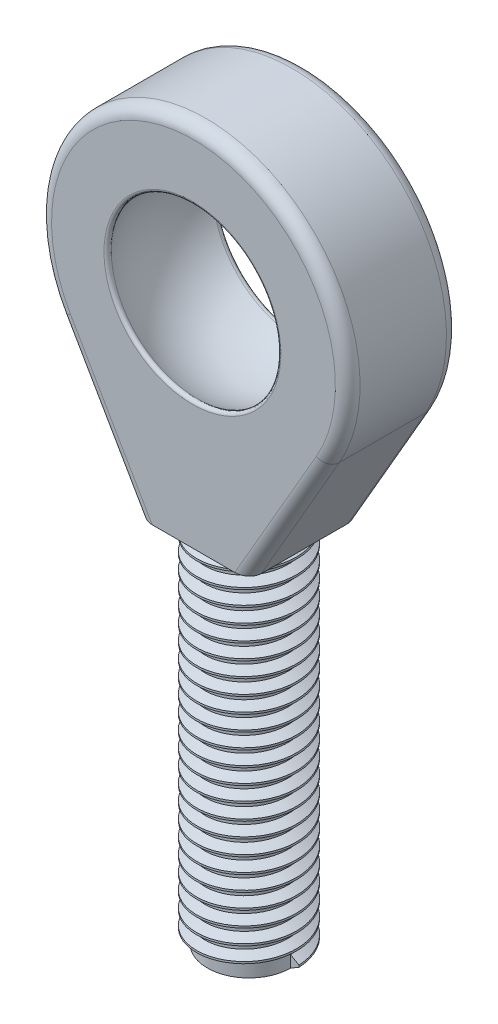
SolidWorks part; units mm, degrees
ref_plane "Спереди" through (0, 0, 0) normal (0, 0, 1) x (1, 0, 0)
ref_plane "Сверху" through (0, 0, 0) normal (0, 1, 0) x (1, 0, 0)
ref_plane "Справа" through (0, 0, 0) normal (1, 0, 0) x (0, 0, -1)
sketch "Эскиз1" plane through (0, 0, 0) normal (0, 0, 1) x (1, 0, 0)
  line L0 (-10.8253, -6.25) -> (-4.5, -17.2058)
  line L1 (4.5, -17.2058) -> (10.8253, -6.25)
  line L2 (-4.5, -17.2058) -> (4.5, -17.2058)
  arc A0 (10.8253, -6.25) -> (-10.8253, -6.25) centre (0, 0) ccw
  point P10 (0, -17.2058)
  dimension "D1" = 25
  dimension "D2" = 60
  dimension "D3" = 9
extrude "Бобышка-Вытянуть1" add sketch "Эскиз1" along normal blind 4.5 and the other way blind 4.5
sketch "Эскиз2" plane through (0, 0, 0) normal (0, 0, 1) x (1, 0, 0)
  line L0 (-0.085, -999.5489) -> (-0.085, 49000.4511) construction
  line L1 (-0.085, 7.9995) -> (-0.085, -7.9995)
  arc A0 (-0.085, -7.9995) -> (-0.085, 7.9995) centre (0, 0) ccw
  dimension "D1" = 16
revolve "Повернуть4" add sketch "Эскиз2" angle 360 about L0
combine bodies "Соединить1" operation type subtract main body 103 bodies to subtract 104
sketch "Эскиз3" plane through (0, -17.2058, 0) normal (0, -1, 0) x (1, 0, 0)
  circle A0 centre (0, 0) radius 3.375
  dimension "D1" = 6.75
extrude "Бобышка-Вытянуть2" add sketch "Эскиз3" along normal blind 30
thread "Резьба2" pitch 1.25 method extrude profile "Профиль резьбы3" start angle 0, offset 0, length 0, pitch 1.25, diameter 6.75
ref_plane "Плоскость3" through (3.375, -47.2058, 0) normal (0, 0, 1) x (1, 0, 0)
sketch "Профиль резьбы3" plane through (3.375, -47.2058, 0) normal (0, 0, 1) x (1, 0, 0)
  line L0 (0, 0) -> (0, 1.25) construction
  line L1 (0, 0) -> (0.6766, 0.3906)
  line L2 (0.6766, 0.3906) -> (0.6766, 0.5469)
  line L3 (0.6766, 0.5469) -> (0, 0.9375)
  line L4 (0.6766, 0.4687) -> (0, 0.4687) construction
  line L11 (0, 0) -> (0, 0.9375)
  point P2 (0, 0)
  dimension "Pitch" = 1.25
  dimension "Profile_Angle" = 60
  dimension "Profile_Land" = 0.1562
  dimension "Profile_Height" = 0.6766
fillet "Скругление1" radius 1 6 edges at (-7.6627, -11.7279, -4.5) (0, 12.5, -4.5) (-7.6627, -11.7279, 4.5) (0, 12.5, 4.5) (7.6627, -11.7279, -4.5) (7.6627, -11.7279, 4.5)
fillet "Скругление2" radius 0.25 2 edges at (1.4775, -6.4893, -4.5) (1.4775, -6.4893, 4.5)
ref_axis "Ось1" through (0, 0, -3.5) along (0, 0, 1)
